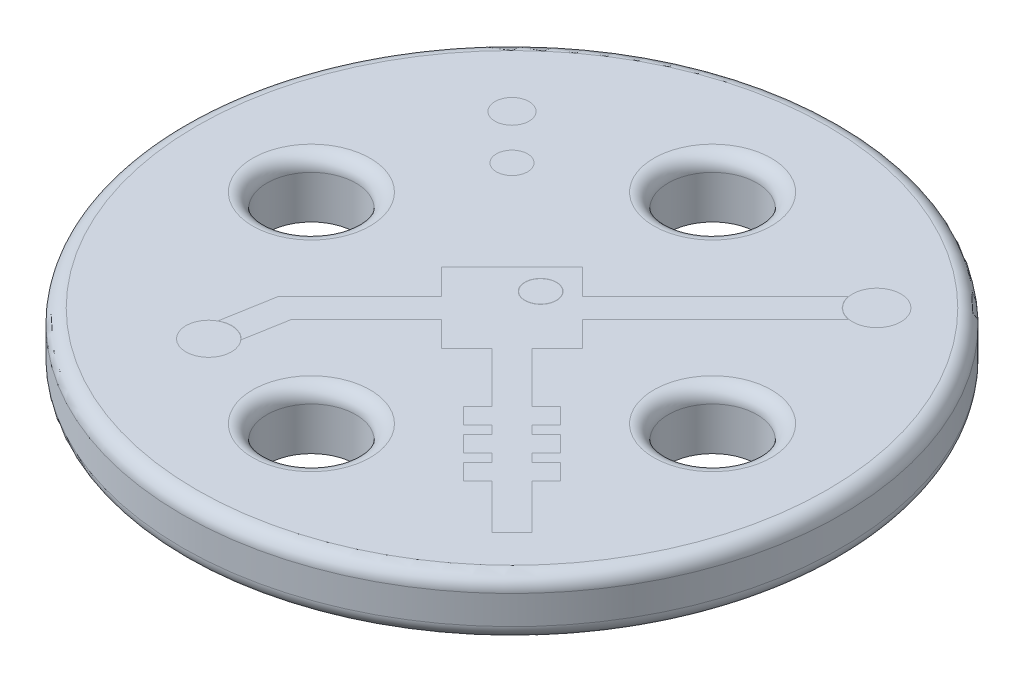
SolidWorks part; units mm, degrees
other "white_4"
other "white_10"
other "white_7"
other "white_6"
other "blue_2"
other "graphite_1"
other "white"
other "white_5"
other "white_8"
other "white_9"
other "white_3"
other "blue_1"
other "white_2"
ref_plane "Front Plane" through (0, 0, 0) normal (0, 0, 1) x (1, 0, 0)
ref_plane "Top Plane" through (0, 0, 0) normal (0, 1, 0) x (1, 0, 0)
ref_plane "Right Plane" through (0, 0, 0) normal (1, 0, 0) x (0, 0, -1)
sketch "Sketch1" plane through (0, 0, 0) normal (0, 1, 0) x (1, 0, 0)
  line L0 (0, 7) -> (0, 0) construction
  circle A0 centre (0, 0) radius 11.5
  circle A1 centre (0, 7) radius 1.55
  circle A2 centre (7, 0) radius 1.55
  circle A3 centre (0, -7) radius 1.55
  circle A4 centre (-7, 0) radius 1.55
  point P14 (0, 0)
  dimension "D1" = 23
  dimension "D2" = 3.1
  dimension "D3" = 7
  dimension "D4" = 4
extrude "Boss-Extrude1" add sketch "Sketch1" along normal blind 2
fillet "Fillet1" radius 0.5 6 edges at (-7, 2, 1.55) (7, 2, 1.55) (0, 2, 11.5) (0, 2, -5.45) (0, 2, 8.55) (0, 0, 11.5)
sketch "Sketch2" [suppressed] plane through (0, 2, 0) normal (0, 1, 0) x (1, 0, 0)
  line L0 (-2.4749, -2.4749) -> (2.4749, 2.4749) construction
  line L3 (-4.2426, -0.7071) -> (0.7071, 4.2426) construction
  line L4 (-0.7071, -4.2426) -> (4.2426, 0.7071) construction
  line L5 (0, 0) -> (23.072, 0) construction
  line L6 (-6.364, -2.1213) -> (-2.1213, -6.364) construction
  line L7 (-2.1213, -6.364) -> (6.364, 2.1213) construction
  line L8 (6.364, 2.1213) -> (2.1213, 6.364) construction
  line L9 (2.1213, 6.364) -> (-6.364, -2.1213) construction
  line L10 (-6.364, -2.1213) -> (6.364, 2.1213) construction
  line L11 (2.1213, 6.364) -> (6.364, 2.1213)
  line L12 (6.364, 2.1213) -> (4.9497, 0.7071)
  line L13 (2.1213, 6.364) -> (0.7071, 4.9497)
  line L14 (-6.364, -2.1213) -> (-4.9497, -0.7071)
  line L15 (-6.364, -2.1213) -> (-2.1213, -6.364)
  line L16 (-2.1213, -6.364) -> (-0.7071, -4.9497)
  circle A0 centre (-7, 0) radius 2.75 construction
  circle A1 centre (0, 7) radius 2.75 construction
  circle A2 centre (7, 0) radius 2.75 construction
  circle A3 centre (0, -7) radius 2.75 construction
  arc A6 (-4.2426, -0.7071) -> (-0.7071, -4.2426) centre (-2.4749, -2.4749) ccw construction
  arc A7 (4.2426, 0.7071) -> (0.7071, 4.2426) centre (2.4749, 2.4749) ccw construction
  circle A8 centre (0, 0) radius 5 construction
  arc A10 (-0.7071, -4.9497) -> (4.9497, 0.7071) centre (0, 0) ccw
  arc A12 (0.7071, 4.9497) -> (-4.9497, -0.7071) centre (0, 0) ccw
  point P13 (0, 0)
  dimension "D1" = 5.5
  dimension "D2" = 12
  dimension "D3" = 5
  dimension "D7" = 10
  dimension "D4" = 45
  dimension "D5" = 6
  dimension "D6" = 12
extrude "Cable hole" [suppressed] cut sketch "Sketch2" against normal through all
fillet "Fillet2" [suppressed] radius 1
sketch "GL_F_side_blue" plane through (0, 0, 0) normal (0, 1, 0) x (1, 0, 0)
  line L0 (4.1012, -5.7912) -> (3.5426, -5.2326)
  line L1 (3.5426, -5.2326) -> (4.0376, -4.7376)
  line L2 (4.0376, -4.7376) -> (3.7477, -4.4477)
  line L3 (3.7477, -4.4477) -> (3.2527, -4.9427)
  line L4 (3.2527, -4.9427) -> (2.6941, -4.3841)
  line L5 (2.6941, -4.3841) -> (3.1891, -3.8891)
  line L6 (3.1891, -3.8891) -> (1.2092, -1.9092)
  line L7 (1.2092, -1.9092) -> (1.3233, -1.795)
  line L8 (1.3233, -1.795) -> (-1.795, -1.795)
  line L9 (-1.795, -1.795) -> (-1.795, 1.3233)
  line L10 (-1.795, 1.3233) -> (-1.9092, 1.2092)
  line L11 (-1.9092, 1.2092) -> (-4.852, 4.1519)
  line L12 (-4.852, 4.1519) -> (-4.7161, 4.1794)
  line L13 (-4.7161, 4.1794) -> (-4.5701, 4.2398)
  line L14 (-4.5701, 4.2398) -> (-4.3805, 4.3805)
  line L15 (-4.3805, 4.3805) -> (-4.2398, 4.5701)
  line L16 (-4.2398, 4.5701) -> (-4.1794, 4.7161)
  line L17 (-4.1794, 4.7161) -> (-4.1519, 4.852)
  line L18 (-4.1519, 4.852) -> (-1.2092, 1.9092)
  line L19 (-1.2092, 1.9092) -> (-1.3233, 1.795)
  line L20 (-1.3233, 1.795) -> (1.3233, 1.795)
  line L21 (1.3233, 1.795) -> (1.2092, 1.9092)
  line L22 (1.2092, 1.9092) -> (5.6637, 6.3638)
  line L23 (5.6637, 6.3638) -> (5.6872, 6.2571)
  line L24 (5.6872, 6.2571) -> (5.7514, 6.1022)
  line L25 (5.7514, 6.1022) -> (5.9008, 5.9008)
  line L26 (5.9008, 5.9008) -> (6.1022, 5.7514)
  line L27 (6.1022, 5.7514) -> (6.2571, 5.6872)
  line L28 (6.2571, 5.6872) -> (6.3638, 5.6637)
  line L29 (6.3638, 5.6637) -> (1.9092, 1.2092)
  line L30 (1.9092, 1.2092) -> (1.795, 1.3233)
  line L31 (1.795, 1.3233) -> (1.795, -1.3233)
  line L32 (1.795, -1.3233) -> (1.9092, -1.2092)
  line L33 (1.9092, -1.2092) -> (3.8891, -3.1891)
  line L34 (3.8891, -3.1891) -> (4.3841, -2.6941)
  line L35 (4.3841, -2.6941) -> (4.9427, -3.2527)
  line L36 (4.9427, -3.2527) -> (4.4477, -3.7477)
  line L37 (4.4477, -3.7477) -> (4.7376, -4.0376)
  line L38 (4.7376, -4.0376) -> (5.2326, -3.5426)
  line L39 (5.2326, -3.5426) -> (5.7912, -4.1012)
  line L40 (5.7912, -4.1012) -> (5.2962, -4.5962)
  line L41 (5.2962, -4.5962) -> (6.9933, -6.2933)
  line L42 (6.9933, -6.2933) -> (6.2933, -6.9933)
  line L43 (6.2933, -6.9933) -> (4.5962, -5.2962)
  line L44 (4.5962, -5.2962) -> (4.1012, -5.7912)
  line L45 (-0.2962, 0.7941) -> (-0.2962, 0.9029)
  line L46 (-0.2962, 0.9029) -> (-0.3174, 1.0096)
  line L47 (-0.3174, 1.0096) -> (-0.359, 1.1102)
  line L48 (-0.359, 1.1102) -> (-0.4195, 1.2006)
  line L49 (-0.4195, 1.2006) -> (-0.4964, 1.2776)
  line L50 (-0.4964, 1.2776) -> (-0.5869, 1.338)
  line L51 (-0.5869, 1.338) -> (-0.6874, 1.3797)
  line L52 (-0.6874, 1.3797) -> (-0.7941, 1.4009)
  line L53 (-0.7941, 1.4009) -> (-0.9029, 1.4009)
  line L54 (-0.9029, 1.4009) -> (-1.0096, 1.3797)
  line L55 (-1.0096, 1.3797) -> (-1.1102, 1.338)
  line L56 (-1.1102, 1.338) -> (-1.2006, 1.2776)
  line L57 (-1.2006, 1.2776) -> (-1.2776, 1.2006)
  line L58 (-1.2776, 1.2006) -> (-1.338, 1.1102)
  line L59 (-1.338, 1.1102) -> (-1.3797, 1.0096)
  line L60 (-1.3797, 1.0096) -> (-1.4009, 0.9029)
  line L61 (-1.4009, 0.9029) -> (-1.4009, 0.7941)
  line L62 (-1.4009, 0.7941) -> (-1.3797, 0.6874)
  line L63 (-1.3797, 0.6874) -> (-1.338, 0.5869)
  line L64 (-1.338, 0.5869) -> (-1.2776, 0.4964)
  line L65 (-1.2776, 0.4964) -> (-1.2006, 0.4195)
  line L66 (-1.2006, 0.4195) -> (-1.1102, 0.359)
  line L67 (-1.1102, 0.359) -> (-1.0096, 0.3174)
  line L68 (-1.0096, 0.3174) -> (-0.9029, 0.2962)
  line L69 (-0.9029, 0.2962) -> (-0.7941, 0.2962)
  line L70 (-0.7941, 0.2962) -> (-0.6874, 0.3174)
  line L71 (-0.6874, 0.3174) -> (-0.5869, 0.359)
  line L72 (-0.5869, 0.359) -> (-0.4964, 0.4195)
  line L73 (-0.4964, 0.4195) -> (-0.4195, 0.4964)
  line L74 (-0.4195, 0.4964) -> (-0.359, 0.5869)
  line L75 (-0.359, 0.5869) -> (-0.3174, 0.6874)
  line L76 (-0.3174, 0.6874) -> (-0.2962, 0.7941)
extrude "GL_F_side_blue_cut" cut sketch "GL_F_side_blue" along normal blind 1.1 from offset 0.5 offset against normal yes
extrude "GL_F_side_blue_inlay" add sketch "GL_F_side_blue<2>" along normal blind 0.6 separate body
sketch "GL_F_side_blue<2>" plane through (0, 0, 0) normal (0, 1, 0) x (1, 0, 0) same geometry as "GL_F_side_blue"
sketch "GL_F_side_white" plane through (0, 0, 0) normal (0, 1, 0) x (1, 0, 0)
  line L0 (-5.628, -6.3839) -> (-5.6958, -6.4665)
  line L1 (-5.6958, -6.4665) -> (-5.7783, -6.5342)
  line L2 (-5.7783, -6.5342) -> (-5.8726, -6.5846)
  line L3 (-5.8726, -6.5846) -> (-5.9748, -6.6156)
  line L4 (-5.9748, -6.6156) -> (-6.0811, -6.6261)
  line L5 (-6.0811, -6.6261) -> (-6.1874, -6.6156)
  line L6 (-6.1874, -6.6156) -> (-6.2897, -6.5846)
  line L7 (-6.2897, -6.5846) -> (-6.3839, -6.5342)
  line L8 (-6.3839, -6.5342) -> (-6.4665, -6.4665)
  line L9 (-6.4665, -6.4665) -> (-6.5342, -6.3839)
  line L10 (-6.5342, -6.3839) -> (-6.5846, -6.2897)
  line L11 (-6.5846, -6.2897) -> (-6.6156, -6.1874)
  line L12 (-6.6156, -6.1874) -> (-6.6261, -6.0811)
  line L13 (-6.6261, -6.0811) -> (-6.6156, -5.9748)
  line L14 (-6.6156, -5.9748) -> (-6.5846, -5.8726)
  line L15 (-6.5846, -5.8726) -> (-6.5342, -5.7783)
  line L16 (-6.5342, -5.7783) -> (-6.4665, -5.6958)
  line L17 (-6.4665, -5.6958) -> (-6.3839, -5.628)
  line L18 (-6.3839, -5.628) -> (-6.2897, -5.5776)
  line L19 (-6.2897, -5.5776) -> (-6.1874, -5.5466)
  line L20 (-6.1874, -5.5466) -> (-6.0811, -5.5361)
  line L21 (-6.0811, -5.5361) -> (-5.9748, -5.5466)
  line L22 (-5.9748, -5.5466) -> (-5.8726, -5.5776)
  line L23 (-5.8726, -5.5776) -> (-5.7783, -5.628)
  line L24 (-5.7783, -5.628) -> (-5.6958, -5.6958)
  line L25 (-5.6958, -5.6958) -> (-5.628, -5.7783)
  line L26 (-5.628, -5.7783) -> (-5.5776, -5.8726)
  line L27 (-5.5776, -5.8726) -> (-5.5466, -5.9748)
  line L28 (-5.5466, -5.9748) -> (-5.5361, -6.0811)
  line L29 (-5.5361, -6.0811) -> (-5.5466, -6.1874)
  line L30 (-5.5466, -6.1874) -> (-5.5776, -6.2897)
  line L31 (-5.5776, -6.2897) -> (-5.628, -6.3839)
  line L32 (-3.7895, -4.5454) -> (-3.8573, -4.628)
  line L33 (-3.8573, -4.628) -> (-3.9399, -4.6958)
  line L34 (-3.9399, -4.6958) -> (-4.0341, -4.7461)
  line L35 (-4.0341, -4.7461) -> (-4.1363, -4.7771)
  line L36 (-4.1363, -4.7771) -> (-4.2426, -4.7876)
  line L37 (-4.2426, -4.7876) -> (-4.349, -4.7771)
  line L38 (-4.349, -4.7771) -> (-4.4512, -4.7461)
  line L39 (-4.4512, -4.7461) -> (-4.5454, -4.6958)
  line L40 (-4.5454, -4.6958) -> (-4.628, -4.628)
  line L41 (-4.628, -4.628) -> (-4.6958, -4.5454)
  line L42 (-4.6958, -4.5454) -> (-4.7461, -4.4512)
  line L43 (-4.7461, -4.4512) -> (-4.7771, -4.349)
  line L44 (-4.7771, -4.349) -> (-4.7876, -4.2426)
  line L45 (-4.7876, -4.2426) -> (-4.7771, -4.1363)
  line L46 (-4.7771, -4.1363) -> (-4.7461, -4.0341)
  line L47 (-4.7461, -4.0341) -> (-4.6958, -3.9399)
  line L48 (-4.6958, -3.9399) -> (-4.628, -3.8573)
  line L49 (-4.628, -3.8573) -> (-4.5454, -3.7895)
  line L50 (-4.5454, -3.7895) -> (-4.4512, -3.7391)
  line L51 (-4.4512, -3.7391) -> (-4.349, -3.7081)
  line L52 (-4.349, -3.7081) -> (-4.2426, -3.6977)
  line L53 (-4.2426, -3.6977) -> (-4.1363, -3.7081)
  line L54 (-4.1363, -3.7081) -> (-4.0341, -3.7391)
  line L55 (-4.0341, -3.7391) -> (-3.9399, -3.7895)
  line L56 (-3.9399, -3.7895) -> (-3.8573, -3.8573)
  line L57 (-3.8573, -3.8573) -> (-3.7895, -3.9399)
  line L58 (-3.7895, -3.9399) -> (-3.7391, -4.0341)
  line L59 (-3.7391, -4.0341) -> (-3.7081, -4.1363)
  line L60 (-3.7081, -4.1363) -> (-3.6977, -4.2426)
  line L61 (-3.6977, -4.2426) -> (-3.7081, -4.349)
  line L62 (-3.7081, -4.349) -> (-3.7391, -4.4512)
  line L63 (-3.7391, -4.4512) -> (-3.7895, -4.5454)
  line L64 (-0.3954, 0.5458) -> (-0.4632, 0.4632)
  line L65 (-0.4632, 0.4632) -> (-0.5458, 0.3954)
  line L66 (-0.5458, 0.3954) -> (-0.64, 0.345)
  line L67 (-0.64, 0.345) -> (-0.7422, 0.314)
  line L68 (-0.7422, 0.314) -> (-0.8485, 0.3036)
  line L69 (-0.8485, 0.3036) -> (-0.9548, 0.314)
  line L70 (-0.9548, 0.314) -> (-1.0571, 0.345)
  line L71 (-1.0571, 0.345) -> (-1.1513, 0.3954)
  line L72 (-1.1513, 0.3954) -> (-1.2339, 0.4632)
  line L73 (-1.2339, 0.4632) -> (-1.3017, 0.5458)
  line L74 (-1.3017, 0.5458) -> (-1.352, 0.64)
  line L75 (-1.352, 0.64) -> (-1.383, 0.7422)
  line L76 (-1.383, 0.7422) -> (-1.3935, 0.8485)
  line L77 (-1.3935, 0.8485) -> (-1.383, 0.9548)
  line L78 (-1.383, 0.9548) -> (-1.352, 1.0571)
  line L79 (-1.352, 1.0571) -> (-1.3017, 1.1513)
  line L80 (-1.3017, 1.1513) -> (-1.2339, 1.2339)
  line L81 (-1.2339, 1.2339) -> (-1.1513, 1.3017)
  line L82 (-1.1513, 1.3017) -> (-1.0571, 1.352)
  line L83 (-1.0571, 1.352) -> (-0.9548, 1.383)
  line L84 (-0.9548, 1.383) -> (-0.8485, 1.3935)
  line L85 (-0.8485, 1.3935) -> (-0.7422, 1.383)
  line L86 (-0.7422, 1.383) -> (-0.64, 1.352)
  line L87 (-0.64, 1.352) -> (-0.5458, 1.3017)
  line L88 (-0.5458, 1.3017) -> (-0.4632, 1.2339)
  line L89 (-0.4632, 1.2339) -> (-0.3954, 1.1513)
  line L90 (-0.3954, 1.1513) -> (-0.345, 1.0571)
  line L91 (-0.345, 1.0571) -> (-0.314, 0.9548)
  line L92 (-0.314, 0.9548) -> (-0.3036, 0.8485)
  line L93 (-0.3036, 0.8485) -> (-0.314, 0.7422)
  line L94 (-0.314, 0.7422) -> (-0.345, 0.64)
  line L95 (-0.345, 0.64) -> (-0.3954, 0.5458)
  line L96 (-4.3876, 4.3876) -> (-4.5081, 4.2887)
  line L97 (-4.5081, 4.2887) -> (-4.6455, 4.2153)
  line L98 (-4.6455, 4.2153) -> (-4.7947, 4.17)
  line L99 (-4.7947, 4.17) -> (-4.9497, 4.1548)
  line L100 (-4.9497, 4.1548) -> (-5.1048, 4.17)
  line L101 (-5.1048, 4.17) -> (-5.254, 4.2153)
  line L102 (-5.254, 4.2153) -> (-5.3914, 4.2887)
  line L103 (-5.3914, 4.2887) -> (-5.5119, 4.3876)
  line L104 (-5.5119, 4.3876) -> (-5.6107, 4.5081)
  line L105 (-5.6107, 4.5081) -> (-5.6842, 4.6455)
  line L106 (-5.6842, 4.6455) -> (-5.7294, 4.7947)
  line L107 (-5.7294, 4.7947) -> (-5.7447, 4.9497)
  line L108 (-5.7447, 4.9497) -> (-5.7294, 5.1048)
  line L109 (-5.7294, 5.1048) -> (-5.6842, 5.254)
  line L110 (-5.6842, 5.254) -> (-5.6107, 5.3914)
  line L111 (-5.6107, 5.3914) -> (-5.5119, 5.5119)
  line L112 (-5.5119, 5.5119) -> (-5.3914, 5.6107)
  line L113 (-5.3914, 5.6107) -> (-5.254, 5.6842)
  line L114 (-5.254, 5.6842) -> (-5.1048, 5.7294)
  line L115 (-5.1048, 5.7294) -> (-4.9497, 5.7447)
  line L116 (-4.9497, 5.7447) -> (-4.7947, 5.7294)
  line L117 (-4.7947, 5.7294) -> (-4.6455, 5.6842)
  line L118 (-4.6455, 5.6842) -> (-4.5081, 5.6107)
  line L119 (-4.5081, 5.6107) -> (-4.3876, 5.5119)
  line L120 (-4.3876, 5.5119) -> (-4.2887, 5.3914)
  line L121 (-4.2887, 5.3914) -> (-4.2153, 5.254)
  line L122 (-4.2153, 5.254) -> (-4.17, 5.1048)
  line L123 (-4.17, 5.1048) -> (-4.1548, 4.9497)
  line L124 (-4.1548, 4.9497) -> (-4.17, 4.7947)
  line L125 (-4.17, 4.7947) -> (-4.2153, 4.6455)
  line L126 (-4.2153, 4.6455) -> (-4.2887, 4.5081)
  line L127 (-4.2887, 4.5081) -> (-4.3876, 4.3876)
  line L128 (7.1029, 5.9079) -> (6.9748, 5.8028)
  line L129 (6.9748, 5.8028) -> (6.8287, 5.7247)
  line L130 (6.8287, 5.7247) -> (6.6702, 5.6766)
  line L131 (6.6702, 5.6766) -> (6.5054, 5.6604)
  line L132 (6.5054, 5.6604) -> (6.3405, 5.6766)
  line L133 (6.3405, 5.6766) -> (6.182, 5.7247)
  line L134 (6.182, 5.7247) -> (6.0359, 5.8028)
  line L135 (6.0359, 5.8028) -> (5.9079, 5.9079)
  line L136 (5.9079, 5.9079) -> (5.8028, 6.0359)
  line L137 (5.8028, 6.0359) -> (5.7247, 6.182)
  line L138 (5.7247, 6.182) -> (5.6766, 6.3405)
  line L139 (5.6766, 6.3405) -> (5.6604, 6.5054)
  line L140 (5.6604, 6.5054) -> (5.6766, 6.6702)
  line L141 (5.6766, 6.6702) -> (5.7247, 6.8287)
  line L142 (5.7247, 6.8287) -> (5.8028, 6.9748)
  line L143 (5.8028, 6.9748) -> (5.9079, 7.1029)
  line L144 (5.9079, 7.1029) -> (6.0359, 7.208)
  line L145 (6.0359, 7.208) -> (6.182, 7.286)
  line L146 (6.182, 7.286) -> (6.3405, 7.3341)
  line L147 (6.3405, 7.3341) -> (6.5054, 7.3504)
  line L148 (6.5054, 7.3504) -> (6.6702, 7.3341)
  line L149 (6.6702, 7.3341) -> (6.8287, 7.286)
  line L150 (6.8287, 7.286) -> (6.9748, 7.208)
  line L151 (6.9748, 7.208) -> (7.1029, 7.1029)
  line L152 (7.1029, 7.1029) -> (7.208, 6.9748)
  line L153 (7.208, 6.9748) -> (7.286, 6.8287)
  line L154 (7.286, 6.8287) -> (7.3341, 6.6702)
  line L155 (7.3341, 6.6702) -> (7.3504, 6.5054)
  line L156 (7.3504, 6.5054) -> (7.3341, 6.3405)
  line L157 (7.3341, 6.3405) -> (7.286, 6.182)
  line L158 (7.286, 6.182) -> (7.208, 6.0359)
  line L159 (7.208, 6.0359) -> (7.1029, 5.9079)
extrude "GL_F_side_white_cut" cut sketch "GL_F_side_white" along normal blind 1.1 from offset 0.5 offset against normal yes
extrude "GL_F_side_white_inlay" add sketch "GL_F_side_white<2>" along normal blind 0.6 separate body
sketch "GL_F_side_white<2>" plane through (0, 0, 0) normal (0, 1, 0) x (1, 0, 0) same geometry as "GL_F_side_white"
sketch "GL_E_side_blue" plane through (0, 0, 0) normal (0, 1, 0) x (1, 0, 0)
  line L0 (4.3841, -6.074) -> (3.8254, -5.5154)
  line L1 (3.8254, -5.5154) -> (4.3204, -5.0205)
  line L2 (4.3204, -5.0205) -> (4.0305, -4.7305)
  line L3 (4.0305, -4.7305) -> (3.5355, -5.2255)
  line L4 (3.5355, -5.2255) -> (2.9769, -4.6669)
  line L5 (2.9769, -4.6669) -> (3.4719, -4.1719)
  line L6 (3.4719, -4.1719) -> (3.182, -3.882)
  line L7 (3.182, -3.882) -> (2.687, -4.377)
  line L8 (2.687, -4.377) -> (2.1284, -3.8184)
  line L9 (2.1284, -3.8184) -> (2.6234, -3.3234)
  line L10 (2.6234, -3.3234) -> (0.8839, -1.5839)
  line L11 (0.8839, -1.5839) -> (0, -2.4678)
  line L12 (0, -2.4678) -> (-0.8839, -1.5839)
  line L13 (-0.8839, -1.5839) -> (-3.4994, -4.1994)
  line L14 (-3.4994, -4.1994) -> (-3.7618, -5.6882)
  line L15 (-3.7618, -5.6882) -> (-3.8485, -5.6032)
  line L16 (-3.8485, -5.6032) -> (-3.9798, -5.5155)
  line L17 (-3.9798, -5.5155) -> (-4.202, -5.436)
  line L18 (-4.202, -5.436) -> (-4.3592, -5.4205)
  line L19 (-4.3592, -5.4205) -> (-4.5164, -5.436)
  line L20 (-4.5164, -5.436) -> (-4.7368, -5.5165)
  line L21 (-4.7368, -5.5165) -> (-4.4202, -3.7202)
  line L22 (-4.4202, -3.7202) -> (-1.5839, -0.8839)
  line L23 (-1.5839, -0.8839) -> (-2.4678, 0)
  line L24 (-2.4678, 0) -> (0, 2.4678)
  line L25 (0, 2.4678) -> (0.8839, 1.5839)
  line L26 (0.8839, 1.5839) -> (5.5223, 6.2223)
  line L27 (5.5223, 6.2223) -> (5.5458, 6.1157)
  line L28 (5.5458, 6.1157) -> (5.6099, 5.9608)
  line L29 (5.6099, 5.9608) -> (5.7593, 5.7593)
  line L30 (5.7593, 5.7593) -> (5.9608, 5.6099)
  line L31 (5.9608, 5.6099) -> (6.1157, 5.5458)
  line L32 (6.1157, 5.5458) -> (6.2223, 5.5223)
  line L33 (6.2223, 5.5223) -> (1.5839, 0.8839)
  line L34 (1.5839, 0.8839) -> (2.4678, 0)
  line L35 (2.4678, 0) -> (1.5839, -0.8839)
  line L36 (1.5839, -0.8839) -> (3.3234, -2.6234)
  line L37 (3.3234, -2.6234) -> (3.8184, -2.1284)
  line L38 (3.8184, -2.1284) -> (4.377, -2.687)
  line L39 (4.377, -2.687) -> (3.882, -3.182)
  line L40 (3.882, -3.182) -> (4.1719, -3.4719)
  line L41 (4.1719, -3.4719) -> (4.6669, -2.9769)
  line L42 (4.6669, -2.9769) -> (5.2255, -3.5355)
  line L43 (5.2255, -3.5355) -> (4.7305, -4.0305)
  line L44 (4.7305, -4.0305) -> (5.0205, -4.3204)
  line L45 (5.0205, -4.3204) -> (5.5154, -3.8254)
  line L46 (5.5154, -3.8254) -> (6.074, -4.3841)
  line L47 (6.074, -4.3841) -> (5.5791, -4.879)
  line L48 (5.5791, -4.879) -> (7.1347, -6.4347)
  line L49 (7.1347, -6.4347) -> (6.4347, -7.1347)
  line L50 (6.4347, -7.1347) -> (4.879, -5.5791)
  line L51 (4.879, -5.5791) -> (4.3841, -6.074)
  line L52 (0.5524, 0.9456) -> (0.5524, 1.0544)
  line L53 (0.5524, 1.0544) -> (0.5311, 1.1611)
  line L54 (0.5311, 1.1611) -> (0.4895, 1.2616)
  line L55 (0.4895, 1.2616) -> (0.429, 1.3521)
  line L56 (0.429, 1.3521) -> (0.3521, 1.429)
  line L57 (0.3521, 1.429) -> (0.2616, 1.4895)
  line L58 (0.2616, 1.4895) -> (0.1611, 1.5311)
  line L59 (0.1611, 1.5311) -> (0.0544, 1.5524)
  line L60 (0.0544, 1.5524) -> (-0.0544, 1.5524)
  line L61 (-0.0544, 1.5524) -> (-0.1611, 1.5311)
  line L62 (-0.1611, 1.5311) -> (-0.2616, 1.4895)
  line L63 (-0.2616, 1.4895) -> (-0.3521, 1.429)
  line L64 (-0.3521, 1.429) -> (-0.429, 1.3521)
  line L65 (-0.429, 1.3521) -> (-0.4895, 1.2616)
  line L66 (-0.4895, 1.2616) -> (-0.5311, 1.1611)
  line L67 (-0.5311, 1.1611) -> (-0.5524, 1.0544)
  line L68 (-0.5524, 1.0544) -> (-0.5524, 0.9456)
  line L69 (-0.5524, 0.9456) -> (-0.5311, 0.8389)
  line L70 (-0.5311, 0.8389) -> (-0.4895, 0.7384)
  line L71 (-0.4895, 0.7384) -> (-0.429, 0.6479)
  line L72 (-0.429, 0.6479) -> (-0.3521, 0.571)
  line L73 (-0.3521, 0.571) -> (-0.2616, 0.5105)
  line L74 (-0.2616, 0.5105) -> (-0.1611, 0.4689)
  line L75 (-0.1611, 0.4689) -> (-0.0544, 0.4476)
  line L76 (-0.0544, 0.4476) -> (0.0544, 0.4476)
  line L77 (0.0544, 0.4476) -> (0.1611, 0.4689)
  line L78 (0.1611, 0.4689) -> (0.2616, 0.5105)
  line L79 (0.2616, 0.5105) -> (0.3521, 0.571)
  line L80 (0.3521, 0.571) -> (0.429, 0.6479)
  line L81 (0.429, 0.6479) -> (0.4895, 0.7384)
  line L82 (0.4895, 0.7384) -> (0.5311, 0.8389)
  line L83 (0.5311, 0.8389) -> (0.5524, 0.9456)
extrude "GL_E_side_blue_cut" cut sketch "GL_E_side_blue" along normal blind 1.1 from offset 1.4
extrude "GL_E_side_blue_inlay" add sketch "GL_E_side_blue<2>" along normal blind 0.6 from offset 1.4 separate body
sketch "GL_E_side_blue<2>" plane through (0, 0, 0) normal (0, 1, 0) x (1, 0, 0) same geometry as "GL_E_side_blue"
sketch "GL_E_side_white" plane through (0, 0, 0) normal (0, 1, 0) x (1, 0, 0)
  line L0 (-3.6982, -6.6672) -> (-3.797, -6.7877)
  line L1 (-3.797, -6.7877) -> (-3.9175, -6.8866)
  line L2 (-3.9175, -6.8866) -> (-4.055, -6.96)
  line L3 (-4.055, -6.96) -> (-4.2041, -7.0053)
  line L4 (-4.2041, -7.0053) -> (-4.3592, -7.0205)
  line L5 (-4.3592, -7.0205) -> (-4.5143, -7.0053)
  line L6 (-4.5143, -7.0053) -> (-4.6634, -6.96)
  line L7 (-4.6634, -6.96) -> (-4.8008, -6.8866)
  line L8 (-4.8008, -6.8866) -> (-4.9213, -6.7877)
  line L9 (-4.9213, -6.7877) -> (-5.0202, -6.6672)
  line L10 (-5.0202, -6.6672) -> (-5.0936, -6.5298)
  line L11 (-5.0936, -6.5298) -> (-5.1389, -6.3806)
  line L12 (-5.1389, -6.3806) -> (-5.1542, -6.2256)
  line L13 (-5.1542, -6.2256) -> (-5.1389, -6.0705)
  line L14 (-5.1389, -6.0705) -> (-5.0936, -5.9213)
  line L15 (-5.0936, -5.9213) -> (-5.0202, -5.7839)
  line L16 (-5.0202, -5.7839) -> (-4.9213, -5.6634)
  line L17 (-4.9213, -5.6634) -> (-4.8008, -5.5646)
  line L18 (-4.8008, -5.5646) -> (-4.6634, -5.4911)
  line L19 (-4.6634, -5.4911) -> (-4.5143, -5.4459)
  line L20 (-4.5143, -5.4459) -> (-4.3592, -5.4306)
  line L21 (-4.3592, -5.4306) -> (-4.2041, -5.4459)
  line L22 (-4.2041, -5.4459) -> (-4.055, -5.4911)
  line L23 (-4.055, -5.4911) -> (-3.9175, -5.5646)
  line L24 (-3.9175, -5.5646) -> (-3.797, -5.6634)
  line L25 (-3.797, -5.6634) -> (-3.6982, -5.7839)
  line L26 (-3.6982, -5.7839) -> (-3.6247, -5.9213)
  line L27 (-3.6247, -5.9213) -> (-3.5795, -6.0705)
  line L28 (-3.5795, -6.0705) -> (-3.5642, -6.2256)
  line L29 (-3.5642, -6.2256) -> (-3.5795, -6.3806)
  line L30 (-3.5795, -6.3806) -> (-3.6247, -6.5298)
  line L31 (-3.6247, -6.5298) -> (-3.6982, -6.6672)
  line L32 (0.4531, 0.6972) -> (0.3854, 0.6146)
  line L33 (0.3854, 0.6146) -> (0.3028, 0.5469)
  line L34 (0.3028, 0.5469) -> (0.2086, 0.4965)
  line L35 (0.2086, 0.4965) -> (0.1063, 0.4655)
  line L36 (0.1063, 0.4655) -> (0, 0.455)
  line L37 (0, 0.455) -> (-0.1063, 0.4655)
  line L38 (-0.1063, 0.4655) -> (-0.2086, 0.4965)
  line L39 (-0.2086, 0.4965) -> (-0.3028, 0.5469)
  line L40 (-0.3028, 0.5469) -> (-0.3854, 0.6146)
  line L41 (-0.3854, 0.6146) -> (-0.4531, 0.6972)
  line L42 (-0.4531, 0.6972) -> (-0.5035, 0.7914)
  line L43 (-0.5035, 0.7914) -> (-0.5345, 0.8937)
  line L44 (-0.5345, 0.8937) -> (-0.545, 1)
  line L45 (-0.545, 1) -> (-0.5345, 1.1063)
  line L46 (-0.5345, 1.1063) -> (-0.5035, 1.2086)
  line L47 (-0.5035, 1.2086) -> (-0.4531, 1.3028)
  line L48 (-0.4531, 1.3028) -> (-0.3854, 1.3854)
  line L49 (-0.3854, 1.3854) -> (-0.3028, 1.4531)
  line L50 (-0.3028, 1.4531) -> (-0.2086, 1.5035)
  line L51 (-0.2086, 1.5035) -> (-0.1063, 1.5345)
  line L52 (-0.1063, 1.5345) -> (0, 1.545)
  line L53 (0, 1.545) -> (0.1063, 1.5345)
  line L54 (0.1063, 1.5345) -> (0.2086, 1.5035)
  line L55 (0.2086, 1.5035) -> (0.3028, 1.4531)
  line L56 (0.3028, 1.4531) -> (0.3854, 1.3854)
  line L57 (0.3854, 1.3854) -> (0.4531, 1.3028)
  line L58 (0.4531, 1.3028) -> (0.5035, 1.2086)
  line L59 (0.5035, 1.2086) -> (0.5345, 1.1063)
  line L60 (0.5345, 1.1063) -> (0.545, 1)
  line L61 (0.545, 1) -> (0.5345, 0.8937)
  line L62 (0.5345, 0.8937) -> (0.5035, 0.7914)
  line L63 (0.5035, 0.7914) -> (0.4531, 0.6972)
  line L64 (-3.9309, 4.0813) -> (-3.9987, 3.9987)
  line L65 (-3.9987, 3.9987) -> (-4.0813, 3.9309)
  line L66 (-4.0813, 3.9309) -> (-4.1755, 3.8806)
  line L67 (-4.1755, 3.8806) -> (-4.2777, 3.8496)
  line L68 (-4.2777, 3.8496) -> (-4.3841, 3.8391)
  line L69 (-4.3841, 3.8391) -> (-4.4904, 3.8496)
  line L70 (-4.4904, 3.8496) -> (-4.5926, 3.8806)
  line L71 (-4.5926, 3.8806) -> (-4.6868, 3.9309)
  line L72 (-4.6868, 3.9309) -> (-4.7694, 3.9987)
  line L73 (-4.7694, 3.9987) -> (-4.8372, 4.0813)
  line L74 (-4.8372, 4.0813) -> (-4.8876, 4.1755)
  line L75 (-4.8876, 4.1755) -> (-4.9186, 4.2777)
  line L76 (-4.9186, 4.2777) -> (-4.929, 4.3841)
  line L77 (-4.929, 4.3841) -> (-4.9186, 4.4904)
  line L78 (-4.9186, 4.4904) -> (-4.8876, 4.5926)
  line L79 (-4.8876, 4.5926) -> (-4.8372, 4.6868)
  line L80 (-4.8372, 4.6868) -> (-4.7694, 4.7694)
  line L81 (-4.7694, 4.7694) -> (-4.6868, 4.8372)
  line L82 (-4.6868, 4.8372) -> (-4.5926, 4.8876)
  line L83 (-4.5926, 4.8876) -> (-4.4904, 4.9186)
  line L84 (-4.4904, 4.9186) -> (-4.3841, 4.929)
  line L85 (-4.3841, 4.929) -> (-4.2777, 4.9186)
  line L86 (-4.2777, 4.9186) -> (-4.1755, 4.8876)
  line L87 (-4.1755, 4.8876) -> (-4.0813, 4.8372)
  line L88 (-4.0813, 4.8372) -> (-3.9987, 4.7694)
  line L89 (-3.9987, 4.7694) -> (-3.9309, 4.6868)
  line L90 (-3.9309, 4.6868) -> (-3.8806, 4.5926)
  line L91 (-3.8806, 4.5926) -> (-3.8496, 4.4904)
  line L92 (-3.8496, 4.4904) -> (-3.8391, 4.3841)
  line L93 (-3.8391, 4.3841) -> (-3.8496, 4.2777)
  line L94 (-3.8496, 4.2777) -> (-3.8806, 4.1755)
  line L95 (-3.8806, 4.1755) -> (-3.9309, 4.0813)
  line L96 (-5.519, 5.519) -> (-5.6091, 5.445)
  line L97 (-5.6091, 5.445) -> (-5.712, 5.39)
  line L98 (-5.712, 5.39) -> (-5.8236, 5.3562)
  line L99 (-5.8236, 5.3562) -> (-5.9397, 5.3447)
  line L100 (-5.9397, 5.3447) -> (-6.0558, 5.3562)
  line L101 (-6.0558, 5.3562) -> (-6.1674, 5.39)
  line L102 (-6.1674, 5.39) -> (-6.2702, 5.445)
  line L103 (-6.2702, 5.445) -> (-6.3604, 5.519)
  line L104 (-6.3604, 5.519) -> (-6.4344, 5.6091)
  line L105 (-6.4344, 5.6091) -> (-6.4894, 5.712)
  line L106 (-6.4894, 5.712) -> (-6.5232, 5.8236)
  line L107 (-6.5232, 5.8236) -> (-6.5347, 5.9397)
  line L108 (-6.5347, 5.9397) -> (-6.5232, 6.0558)
  line L109 (-6.5232, 6.0558) -> (-6.4894, 6.1674)
  line L110 (-6.4894, 6.1674) -> (-6.4344, 6.2702)
  line L111 (-6.4344, 6.2702) -> (-6.3604, 6.3604)
  line L112 (-6.3604, 6.3604) -> (-6.2702, 6.4344)
  line L113 (-6.2702, 6.4344) -> (-6.1674, 6.4894)
  line L114 (-6.1674, 6.4894) -> (-6.0558, 6.5232)
  line L115 (-6.0558, 6.5232) -> (-5.9397, 6.5347)
  line L116 (-5.9397, 6.5347) -> (-5.8236, 6.5232)
  line L117 (-5.8236, 6.5232) -> (-5.712, 6.4894)
  line L118 (-5.712, 6.4894) -> (-5.6091, 6.4344)
  line L119 (-5.6091, 6.4344) -> (-5.519, 6.3604)
  line L120 (-5.519, 6.3604) -> (-5.445, 6.2702)
  line L121 (-5.445, 6.2702) -> (-5.39, 6.1674)
  line L122 (-5.39, 6.1674) -> (-5.3562, 6.0558)
  line L123 (-5.3562, 6.0558) -> (-5.3447, 5.9397)
  line L124 (-5.3447, 5.9397) -> (-5.3562, 5.8236)
  line L125 (-5.3562, 5.8236) -> (-5.39, 5.712)
  line L126 (-5.39, 5.712) -> (-5.445, 5.6091)
  line L127 (-5.445, 5.6091) -> (-5.519, 5.519)
  line L128 (6.9614, 5.7665) -> (6.8334, 5.6614)
  line L129 (6.8334, 5.6614) -> (6.6873, 5.5833)
  line L130 (6.6873, 5.5833) -> (6.5288, 5.5352)
  line L131 (6.5288, 5.5352) -> (6.364, 5.519)
  line L132 (6.364, 5.519) -> (6.1991, 5.5352)
  line L133 (6.1991, 5.5352) -> (6.0406, 5.5833)
  line L134 (6.0406, 5.5833) -> (5.8945, 5.6614)
  line L135 (5.8945, 5.6614) -> (5.7665, 5.7665)
  line L136 (5.7665, 5.7665) -> (5.6614, 5.8945)
  line L137 (5.6614, 5.8945) -> (5.5833, 6.0406)
  line L138 (5.5833, 6.0406) -> (5.5352, 6.1991)
  line L139 (5.5352, 6.1991) -> (5.519, 6.364)
  line L140 (5.519, 6.364) -> (5.5352, 6.5288)
  line L141 (5.5352, 6.5288) -> (5.5833, 6.6873)
  line L142 (5.5833, 6.6873) -> (5.6614, 6.8334)
  line L143 (5.6614, 6.8334) -> (5.7665, 6.9614)
  line L144 (5.7665, 6.9614) -> (5.8945, 7.0665)
  line L145 (5.8945, 7.0665) -> (6.0406, 7.1446)
  line L146 (6.0406, 7.1446) -> (6.1991, 7.1927)
  line L147 (6.1991, 7.1927) -> (6.364, 7.2089)
  line L148 (6.364, 7.2089) -> (6.5288, 7.1927)
  line L149 (6.5288, 7.1927) -> (6.6873, 7.1446)
  line L150 (6.6873, 7.1446) -> (6.8334, 7.0665)
  line L151 (6.8334, 7.0665) -> (6.9614, 6.9614)
  line L152 (6.9614, 6.9614) -> (7.0665, 6.8334)
  line L153 (7.0665, 6.8334) -> (7.1446, 6.6873)
  line L154 (7.1446, 6.6873) -> (7.1927, 6.5288)
  line L155 (7.1927, 6.5288) -> (7.2089, 6.364)
  line L156 (7.2089, 6.364) -> (7.1927, 6.1991)
  line L157 (7.1927, 6.1991) -> (7.1446, 6.0406)
  line L158 (7.1446, 6.0406) -> (7.0665, 5.8945)
  line L159 (7.0665, 5.8945) -> (6.9614, 5.7665)
extrude "GL_E_side_white_cut" cut sketch "GL_E_side_white" along normal blind 1.1 from offset 1.4
extrude "GL_E_side_white_inlay" add sketch "GL_E_side_white<2>" along normal blind 0.6 from offset 1.4 separate body
sketch "GL_E_side_white<2>" plane through (0, 0, 0) normal (0, 1, 0) x (1, 0, 0) same geometry as "GL_E_side_white"
